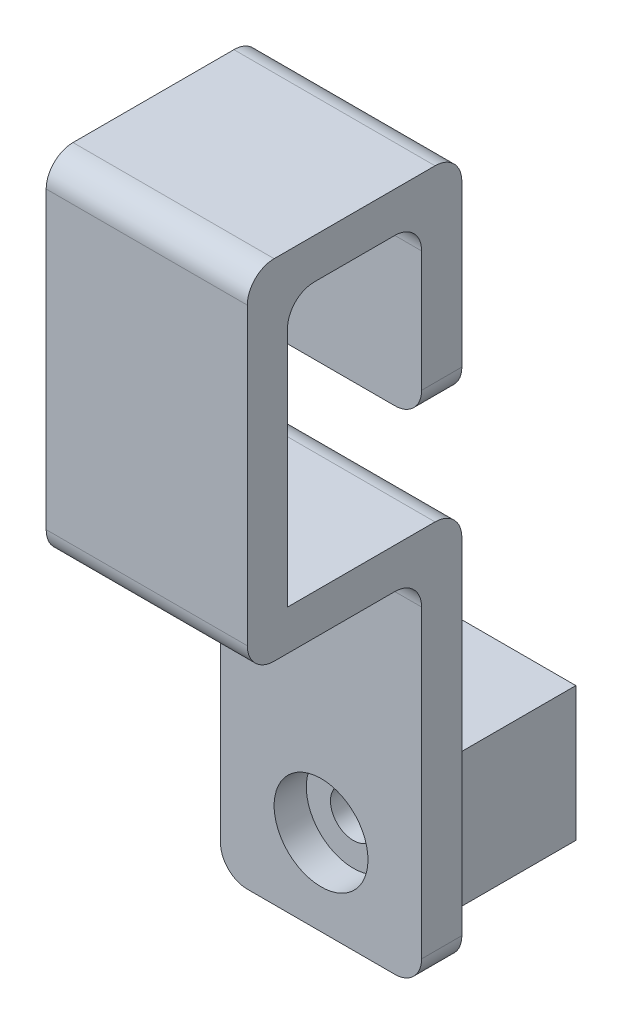
SolidWorks part; units mm, degrees
ref_plane "Płaszczyzna przednia" through (0, 0, 0) normal (0, 0, 1) x (1, 0, 0)
ref_plane "Płaszczyzna górna" through (0, 0, 0) normal (0, 1, 0) x (1, 0, 0)
ref_plane "Płaszczyzna prawa" through (0, 0, 0) normal (1, 0, 0) x (0, 0, -1)
sketch "Szkic1" plane through (0, 0, 0) normal (0, 0, 1) x (1, 0, 0)
  line L1 (-5, 5) -> (5, 5)
  line L2 (-5, 5) -> (-5, -5)
  line L3 (-5, -5) -> (5, -5)
  line L4 (5, 5) -> (5, -5)
  line L5 (-5, 5) -> (5, -5) construction
  line L6 (-5, -5) -> (5, 5) construction
  point P0 (0, 0)
  dimension "D1" = 10
  dimension "D2" = 10
extrude "Dodanie-wyciągnięcie1" add sketch "Szkic1" along normal blind 11
sketch "Szkic2" plane through (0, 0, 11) normal (0, 0, 1) x (1, 0, 0)
  line L0 (-5, -5) -> (5, -5) construction
  line L1 (-7.5, -6.4012) -> (7.5, -6.4012)
  line L2 (-7.5, -6.4012) -> (-7.5, 23.3205)
  line L3 (-7.5, 23.3205) -> (7.5, 23.3205)
  line L4 (7.5, -6.4012) -> (7.5, 23.3205)
  line L5 (-7.5, -6.4012) -> (7.5, 23.3205) construction
  line L6 (-7.5, 23.3205) -> (7.5, -6.4012) construction
  point P4 (0, 8.4597)
  point P5 (0, -5)
  point P10 (-10.861, 2.1623)
  dimension "D1" = 15
  dimension "D2" = 29.7217
  dimension "D3" = 0
extrude "Dodanie-wyciągnięcie2" add sketch "Szkic2" along normal blind 3
sketch "Szkic3" plane through (0, 0, 14) normal (0, 0, 1) x (1, 0, 0)
  line L0 (7.5, -6.4012) -> (7.5, 23.3205) construction
  line L1 (-7.5, 23.3205) -> (7.5, 23.3205)
  line L2 (-7.5, 23.3205) -> (-7.5, 20.3205)
  line L3 (-7.5, 20.3205) -> (7.5, 20.3205)
  line L4 (7.5, 23.3205) -> (7.5, 20.3205)
  line L5 (-7.5, 23.3205) -> (7.5, 20.3205) construction
  line L6 (-7.5, 20.3205) -> (7.5, 23.3205) construction
  point P4 (0, 21.8205)
  dimension "D1" = 3
extrude "Dodanie-wyciągnięcie3" add sketch "Szkic3" along normal blind 13
sketch "Szkic4" plane through (0, 0, 14) normal (0, 0, 1) x (1, 0, 0)
  point P0 (0, 0)
hole_wizard "Pogłębienie walcowe pod M3 Śrubę z łbem stożkowym ściętym1" positions "Szkic 3D1" profile "Szkic5" counterbore size "M3" standard "ISO" end condition up to next
sketch3d "Szkic 3D1"
  point P0 (0, 0, 14)
sketch "Szkic5" plane through (0, 0, 14) normal (1, 0, 0) x (0, -1, 0)
  line L0 (0, 0) -> (0, 14)
  line L1 (0, 14) -> (1.7, 14)
  line L3 (1.7, 14) -> (1.7, 2.4)
  line L4 (1.7, 2.4) -> (3.5, 2.4)
  line L5 (3.5, 2.4) -> (3.5, 0)
  line L7 (3.5, 0) -> (0, 0)
  line L11 (0, -6.35) -> (0, 107.95) construction
  dimension "Średnica otworu na wylot" = 3.4
  dimension "Głębokość otworu na wylot" = 14
  dimension "Średnica pogłębienia walcowego" = 7
  dimension "Głębokość pogłębienia walcowego" = 2.4
fillet "Zaokrąglenie1" radius 2 2 edges at (-7.5, -6.4012, 12.5) (7.5, -6.4012, 12.5)
fillet "Zaokrąglenie2" radius 2 2 edges at (0, 23.3205, 11)
sketch "Szkic6" plane through (0, 23.3205, 0) normal (0, 1, 0) x (1, 0, 0)
  line L0 (-7.5, -27) -> (-7.5, -13) construction
  line L1 (7.5, -27) -> (-7.5, -27)
  line L2 (7.5, -27) -> (7.5, -24)
  line L3 (7.5, -24) -> (-7.5, -24)
  line L4 (-7.5, -27) -> (-7.5, -24)
  line L5 (7.5, -27) -> (-7.5, -24) construction
  line L6 (7.5, -24) -> (-7.5, -27) construction
  point P4 (0, -25.5)
  dimension "D1" = 3
extrude "Dodanie-wyciągnięcie4" add sketch "Szkic6" along normal blind 23
sketch "Szkic7" plane through (0, 0, 24) normal (0, 0, -1) x (-1, 0, 0)
  line L0 (7.5, 46.3205) -> (7.5, 23.3205) construction
  line L1 (-7.5, 46.3205) -> (7.5, 46.3205)
  line L2 (-7.5, 46.3205) -> (-7.5, 43.3205)
  line L3 (-7.5, 43.3205) -> (7.5, 43.3205)
  line L4 (7.5, 46.3205) -> (7.5, 43.3205)
  line L5 (-7.5, 46.3205) -> (7.5, 43.3205) construction
  line L6 (-7.5, 43.3205) -> (7.5, 46.3205) construction
  point P4 (0, 44.8205)
  dimension "D1" = 3
extrude "Dodanie-wyciągnięcie5" add sketch "Szkic7" along normal blind 13
sketch "Szkic8" plane through (0, 43.3205, 0) normal (0, -1, 0) x (1, 0, 0)
  line L0 (-7.5, 11) -> (-7.5, 24) construction
  line L1 (7.5, 11) -> (-7.5, 11)
  line L2 (7.5, 11) -> (7.5, 14)
  line L3 (7.5, 14) -> (-7.5, 14)
  line L4 (-7.5, 11) -> (-7.5, 14)
  line L5 (7.5, 11) -> (-7.5, 14) construction
  line L6 (7.5, 14) -> (-7.5, 11) construction
  point P4 (0, 12.5)
  dimension "D1" = 3
extrude "Dodanie-wyciągnięcie6" add sketch "Szkic8" along normal blind 13
fillet "Zaokrąglenie3" radius 2 5 edges at (0, 46.3205, 11) (0, 46.3205, 27) (0, 20.3205, 27) (0, 43.3205, 24) (0, 43.3205, 14)
fillet "Zaokrąglenie4" radius 2 2 edges at (7.5, 30.3205, 12.5) (-7.5, 30.3205, 12.5)
